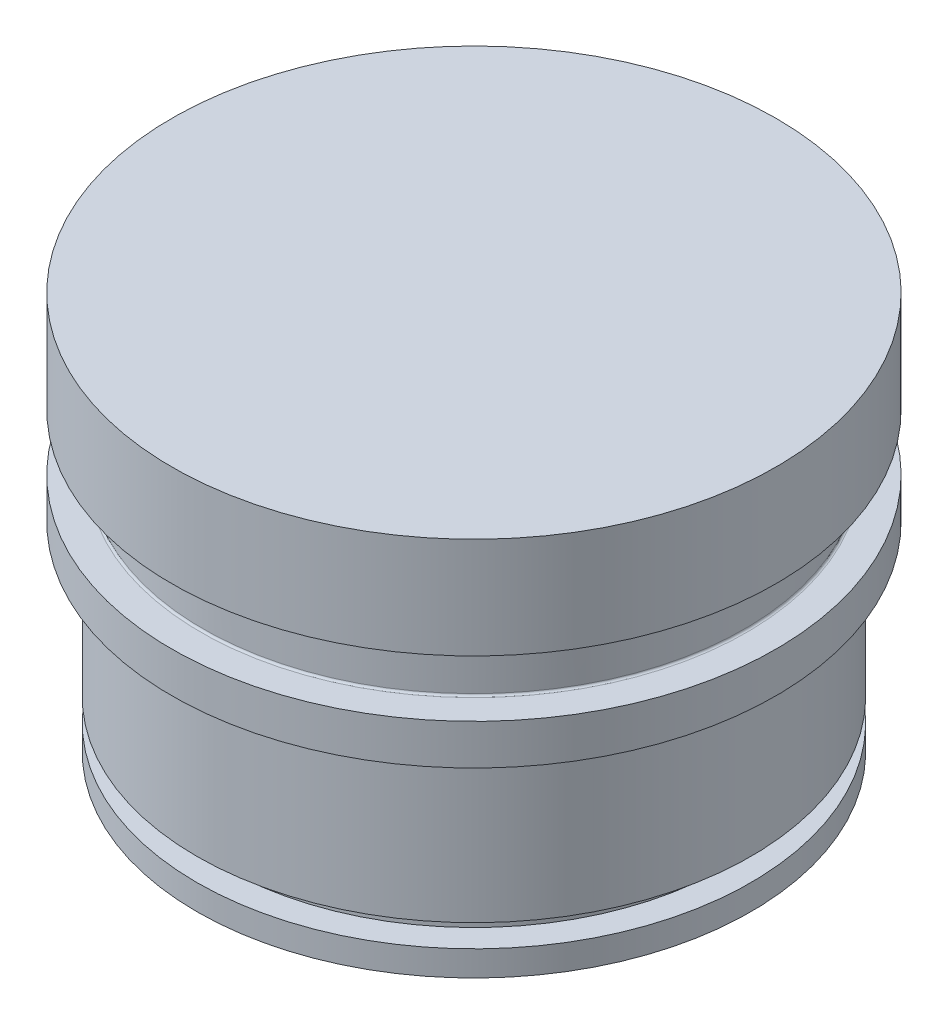
SolidWorks part; units mm, degrees
material "PVC Rigid"
ref_plane "Front Plane" through (0, 0, 0) normal (0, 0, 1) x (1, 0, 0)
ref_plane "Top Plane" through (0, 0, 0) normal (0, 1, 0) x (1, 0, 0)
ref_plane "Right Plane" through (0, 0, 0) normal (1, 0, 0) x (0, 0, -1)
sketch "Sketch1" plane through (0, 0, 0) normal (0, 0, 1) x (1, 0, 0)
  line L0 (0, 0) -> (0, 135.9298) construction
  line L1 (0, 0) -> (-17.399, 0)
  line L2 (-17.399, 0) -> (-17.399, 1.5875)
  line L3 (-17.399, 1.5875) -> (-15.7607, 1.5875)
  line L4 (-15.7607, 1.5875) -> (-15.7607, 3.0099)
  line L5 (-15.7607, 3.0099) -> (-17.399, 3.0099)
  line L6 (-17.399, 3.0099) -> (-17.399, 12.5349)
  line L7 (-17.399, 12.5349) -> (-18.9738, 12.5349)
  line L8 (-18.9738, 12.5349) -> (-18.9738, 15.0749)
  line L9 (-18.9738, 15.0749) -> (-17.018, 15.0749)
  line L10 (-17.018, 15.0749) -> (-17.018, 18.6309)
  line L11 (-17.018, 18.6309) -> (-18.9738, 18.6309)
  line L12 (-18.9738, 18.6309) -> (-18.9738, 24.9809)
  line L13 (-18.9738, 24.9809) -> (0, 24.9809)
  line L18 (-19.05, 9.1791) -> (-19.05, 29.9268) construction
  line L19 (-19.0881, 9.1791) -> (-19.0881, 29.9268) construction
  line L20 (-17.018, 16.8529) -> (-18.2245, 16.8529) construction
  line L21 (-18.2245, 16.8529) -> (-18.3642, 16.8529) construction
  line L28 (-17.399, 12.5349) -> (-13.97, 12.5349) construction
  line L42 (0, 24.9809) -> (0, 0)
  circle A0 centre (-18.3642, 16.8529) radius 1.3462 construction
  circle A1 centre (-18.2245, 16.8529) radius 1.27 construction
  point P29 (-19.4945, 16.8529)
  point P30 (-16.9545, 16.8529)
  point P31 (-19.7104, 16.8529)
  dimension "D4" = 2.54
  dimension "D5" = 2.6924
  dimension "D1" = 38.1
  dimension "D2" = 38.1762
  dimension "D3" = 0.0635
  dimension "D6" = 2.54
  dimension "D7" = 37.9476
  dimension "D8" = 17.399
  dimension "D9" = 34.036
  dimension "D10" = 0.4064
  dimension "D11" = 0.6223
  dimension "D12" = 9.525
  dimension "D13" = 12.446
  dimension "D15" = 1.5875
  dimension "D16" = 15.7607
  dimension "D17" = 1.4224
  dimension "D18" = 3.556
revolve "Revolve1" add sketch "Sketch1" angle 360 about L0
ref_axis "Axis1" through (0, -6.183, 0) along (0, 1, 0)
fillet "Fillet4" radius 0.127 2 edges at (0, 15.0749, -17.018) (0, 18.6309, -17.018)
